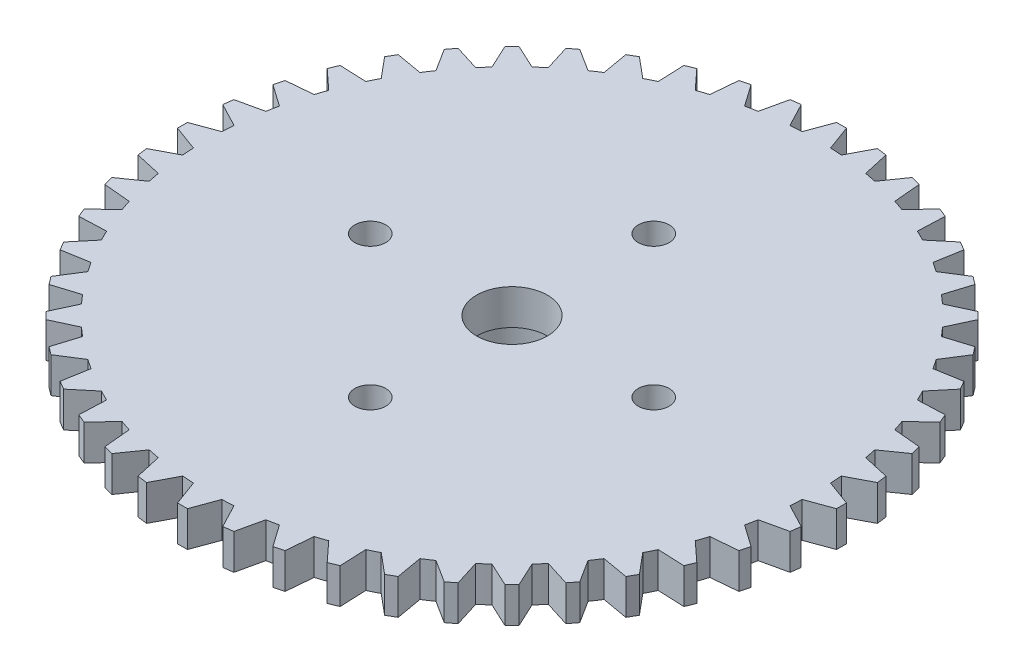
SolidWorks part; units mm, degrees
material "ABS"
ref_plane "Front" through (0, 0, 0) normal (0, 0, 1) x (1, 0, 0)
ref_plane "Top" through (0, 0, 0) normal (0, 1, 0) x (1, 0, 0)
ref_plane "Right" through (0, 0, 0) normal (1, 0, 0) x (0, 0, -1)
sketch "Sketch2" plane through (0, 0, 0) normal (0, 1, 0) x (1, 0, 0)
  circle A0 centre (0, 0) radius 21.5
  circle A1 centre (0, 0) radius 2.5
  dimension "D1" = 43
  dimension "D2" = 5
extrude "Boss-Extrude1" add sketch "Sketch2" along normal blind 2.5
ref_plane "Plane1" through (0, 0, 0) normal (0, 1, 0) x (1, 0, 0)
sketch "Sketch3" plane through (0, 0, 0) normal (0, 1, 0) x (1, 0, 0)
  line L0 (0, 21.5) -> (0, -21.5) construction
  line L1 (-21.5, 0) -> (21.5, 0) construction
  line L3 (0, 21.5) -> (0, 23.25) construction
  line L4 (-1, 21.4767) -> (-0.35, 23.25)
  line L5 (-0.35, 23.25) -> (0.35, 23.25)
  line L6 (1, 21.4767) -> (0.35, 23.25)
  circle A0 centre (0, 0) radius 21.5 construction
  arc A1 (-21.5, 0) -> (21.5, 0) centre (0, 0) ccw
  arc A2 (1, 21.4767) -> (-1, 21.4767) centre (0, 0) ccw
  dimension "D1" = 2
  dimension "D2" = 0.35
  dimension "D3" = 23.25
extrude "Boss-Extrude2" add sketch "Sketch3" along normal blind 2.5 contours L6 L5 L4 A2
pattern_circular "CirPattern1" count 48 over 360 about axis through (0, 2.5, 0) along (0, 1, 0) of "Boss-Extrude2"
ref_plane "Plane2" through (0, 2.5, 0) normal (0, 1, 0) x (1, 0, 0)
sketch "Sketch5" plane through (0, 2.5, 0) normal (0, 1, 0) x (1, 0, 0)
  line L0 (-34.259, 0) -> (34.259, 0) construction
  line L1 (0, -34.259) -> (0, 34.259) construction
  circle A0 centre (0, 10) radius 1.09
  point P6 (0, 0)
  dimension "D1" = 10
  dimension "D2" = 2.18
extrude "Cut-Extrude2" cut sketch "Sketch5" against normal up to surface (2.5 mm away) up to face at (0, 0, 0)
pattern_circular "CirPattern2" count 4 over 360 of "Cut-Extrude2"
sketch "Sketch6" plane through (0, 0, 0) normal (0, -1, 0) x (-1, 0, 0)
  circle A0 centre (0, 0) radius 3.15
  circle A1 centre (0, 0) radius 2.8
  dimension "D1" = 6.3
  dimension "D2" = 5.6
extrude "Boss-Extrude3" add sketch "Sketch6" along normal blind 3
